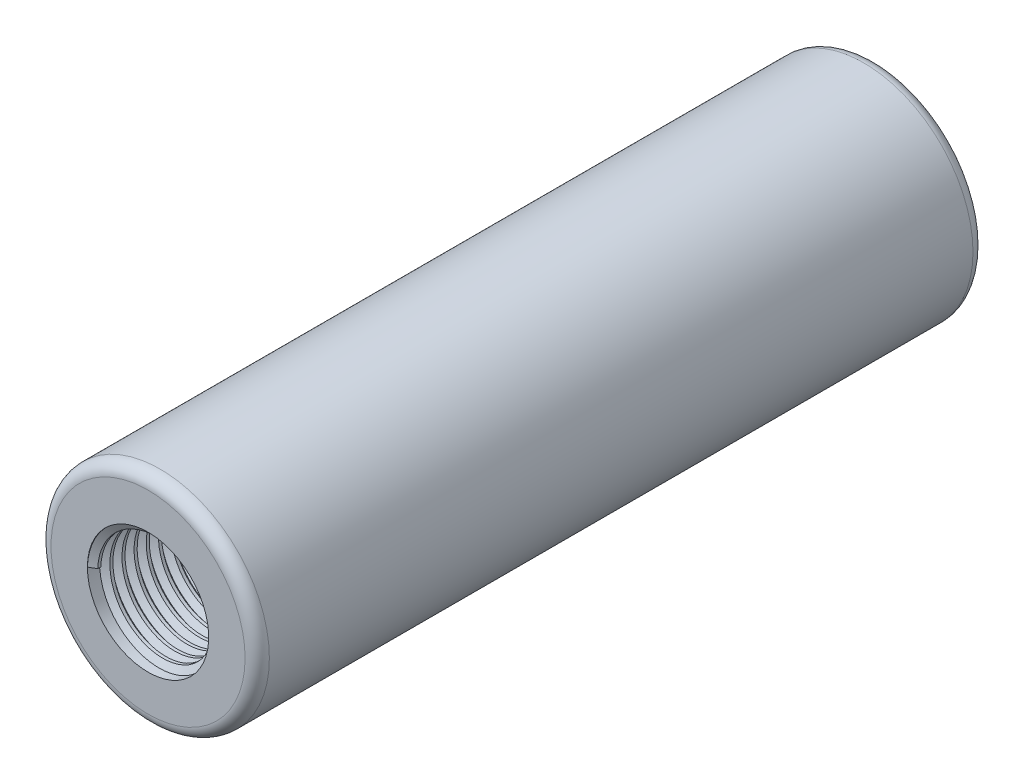
SolidWorks part; units mm, degrees
ref_plane "Front Plane" through (0, 0, 0) normal (0, 0, 1) x (1, 0, 0)
ref_plane "Top Plane" through (0, 0, 0) normal (0, 1, 0) x (1, 0, 0)
ref_plane "Right Plane" through (0, 0, 0) normal (1, 0, 0) x (0, 0, -1)
sketch "Sketch1" plane through (0, 0, 0) normal (0, 0, 1) x (1, 0, 0)
  circle A0 centre (0, 0) radius 5
  circle A1 centre (0, 0) radius 9
  dimension "D1" = 18
  dimension "D2" = 10
extrude "Boss-Extrude1" add sketch "Sketch1" along normal mid plane 60 contours A0 | A1 region at (0, 0, 0)
fillet "Fillet1" radius 1 2 edges at (9, 0, -30) (9, 0, 30)
thread "Thread1" pitch 1 method extrude profile "Thread Profile1" start angle 0, offset 0, length 10, pitch 1, diameter 10
ref_plane "Plane1" through (5, 0, -30) normal (0, -1, 0) x (1, 0, 0)
sketch "Thread Profile1" plane through (5, 0, -30) normal (0, -1, 0) x (1, 0, 0)
  line L0 (0, 0) -> (0, 1) construction
  line L11 (0, 0) -> (0, 0.875)
  line L12 (0, 0.875) -> (-0.5413, 0.5625)
  line L13 (-0.5413, 0.5625) -> (-0.5413, 0.3125)
  line L15 (-0.5413, 0.3125) -> (0, 0)
  line L17 (-0.5413, 0.4375) -> (0, 0.4375) construction
  point P2 (0, 0)
  dimension "Pitch" = 1
  dimension "Profile_Angle" = 60
  dimension "Profile_Land" = 0.25
  dimension "Profile_Height" = 0.5413
thread "Thread2" pitch 1 method extrude profile "Thread Profile2" start angle 0, offset 0, length 10, pitch 1, diameter 10
ref_plane "Plane2" through (-5, 0, 30) normal (0, -1, 0) x (-1, 0, 0)
sketch "Thread Profile2" plane through (-5, 0, 30) normal (0, -1, 0) x (-1, 0, 0)
  line L0 (0, 0) -> (0, 1) construction
  line L11 (0, 0) -> (0, 0.875)
  line L12 (0, 0.875) -> (-0.5413, 0.5625)
  line L13 (-0.5413, 0.5625) -> (-0.5413, 0.3125)
  line L15 (-0.5413, 0.3125) -> (0, 0)
  line L17 (-0.5413, 0.4375) -> (0, 0.4375) construction
  point P2 (0, 0)
  dimension "Pitch" = 1
  dimension "Profile_Angle" = 60
  dimension "Profile_Land" = 0.25
  dimension "Profile_Height" = 0.5413
